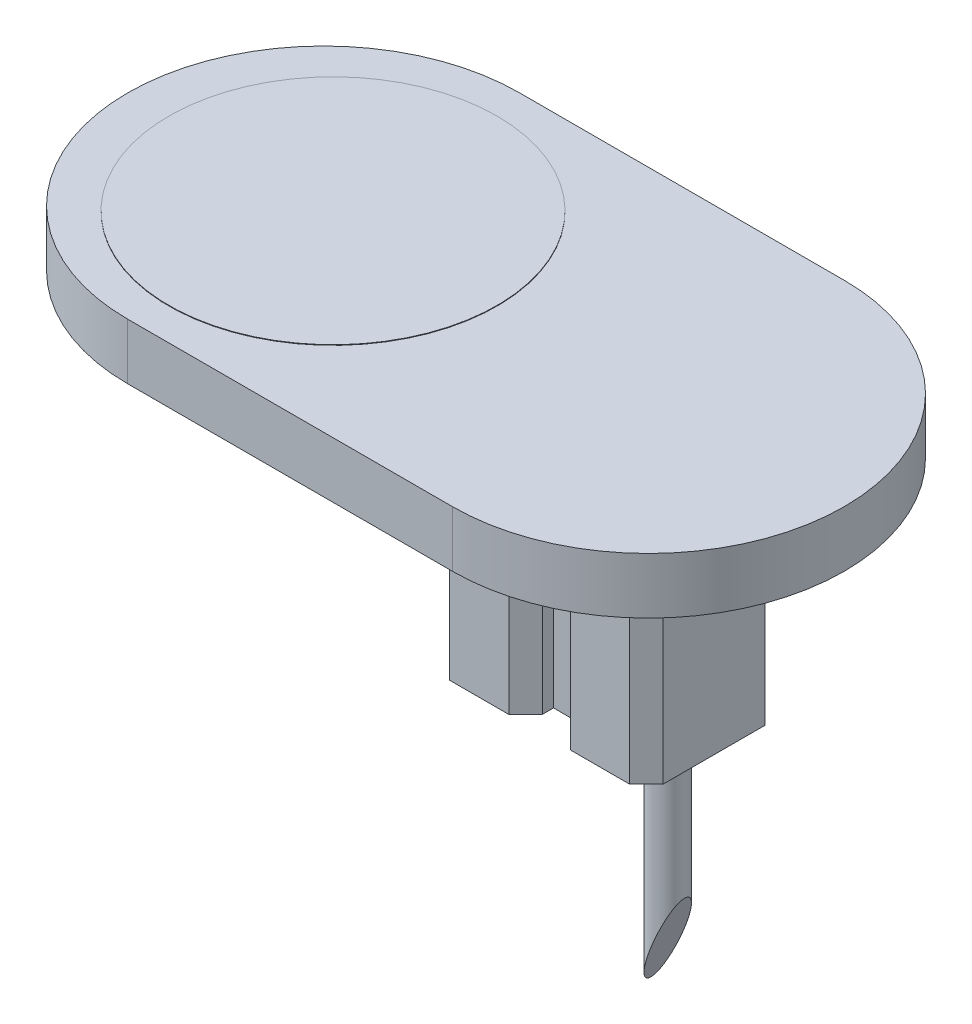
SolidWorks part; units mm, degrees
ref_plane "前视基准面" through (0, 0, 0) normal (0, 0, 1) x (1, 0, 0)
ref_plane "上视基准面" through (0, 0, 0) normal (0, 1, 0) x (1, 0, 0)
ref_plane "右视基准面" through (0, 0, 0) normal (1, 0, 0) x (0, 0, -1)
sketch "草图1" plane through (0, 0, 0) normal (0, 1, 0) x (1, 0, 0)
  line L0 (-8.8189, 0) -> (-3.0189, 0) construction
  line L1 (-8.8189, 3.5) -> (-3.0189, 3.5)
  line L2 (-8.8189, -3.5) -> (-3.0189, -3.5)
  arc A0 (-8.8189, 3.5) -> (-8.8189, -3.5) centre (-8.8189, 0) ccw
  arc A1 (-3.0189, -3.5) -> (-3.0189, 3.5) centre (-3.0189, 0) ccw
  point P3 (-5.9189, 0)
  dimension "D2" = 3.5
  dimension "D1" = 5.8
extrude "凸台-拉伸1" add sketch "草图1" along normal blind 1
sketch "草图2" plane through (0, 1, 0) normal (0, 1, 0) x (1, 0, 0)
  circle A0 centre (-8.6515, 0) radius 2.9305
extrude "凸台-拉伸2" add sketch "草图2" along normal blind 0.01 contours A0
sketch "草图3" plane through (0, 0, 0) normal (0, -1, 0) x (-1, 0, 0)
  line L0 (12.3189, 0) -> (5.6584, 0) construction
  line L1 (5.6584, -1.2107) -> (1.8446, -1.2107)
  line L2 (5.6584, -1.2107) -> (5.6584, 1.2107)
  line L3 (5.6584, 1.2107) -> (1.8446, 1.2107)
  line L4 (1.8446, -1.2107) -> (1.8446, 1.2107)
  arc A0 (8.8189, -3.5) -> (8.8189, 3.5) centre (8.8189, 0) ccw construction
extrude "凸台-拉伸3" add sketch "草图3" along normal blind 4
sketch "草图4" plane through (0, 0, -1.2107) normal (0, 0, -1) x (-1, 0, 0)
  line L0 (5.6584, -4) -> (1.8446, -4) construction
  line L1 (4.0015, -4) -> (3.5015, -4)
  line L2 (4.0015, -4) -> (4.0015, 0)
  line L3 (4.0015, 0) -> (3.5015, 0)
  line L4 (3.5015, -4) -> (3.5015, 0)
  line L5 (5.6584, 0) -> (1.8446, 0) construction
  line L6 (5.6584, -2) -> (4.0015, -2) construction
  line L7 (5.6584, -4) -> (5.6584, 0) construction
  line L8 (3.5015, -2) -> (1.8446, -2) construction
  line L9 (1.8446, -4) -> (1.8446, 0) construction
  dimension "D1" = 0.5
extrude "切除-拉伸1" cut sketch "草图4" against normal blind 0.3
sketch "草图5" plane through (0, 0, 1.2107) normal (0, 0, 1) x (1, 0, 0)
  line L1 (-3.5015, -4) -> (-4.0015, -4)
  line L2 (-3.5015, -4) -> (-3.5015, 0)
  line L3 (-3.5015, 0) -> (-4.0015, 0)
  line L4 (-4.0015, -4) -> (-4.0015, 0)
extrude "切除-拉伸2" cut sketch "草图5" against normal blind 0.5
chamfer "倒角1" distance 0.3 angle 45 8 edges at (-1.8446, -2, -1.2107) (-5.6584, -2, -1.2107) (-5.6584, -2, 1.2107) (-1.8446, -2, 1.2107) (-4.0015, -2, -1.2107) (-3.5015, -2, -1.2107) (-4.0015, -2, 1.2107) (-3.5015, -2, 1.2107)
sketch "草图6" plane through (0, -4, 0) normal (0, -1, 0) x (-1, 0, 0)
  line L0 (2.673, 0) -> (2.673, 1.2107) construction
  line L1 (3.2015, 1.2107) -> (2.1446, 1.2107) construction
  line L2 (2.673, 0) -> (1.8446, 0) construction
  line L3 (1.8446, 0.9107) -> (1.8446, -0.9107) construction
  circle A0 centre (2.673, 0) radius 0.3
  dimension "D1" = 0.6
extrude "凸台-拉伸4" add sketch "草图6" along normal blind 4
sketch "草图7" plane through (0, 0, 0) normal (0, 0, 1) x (1, 0, 0)
  line L0 (-2.973, -8) -> (-2.373, -6.4852)
  line L1 (-2.373, -8) -> (-2.373, -4) construction
  line L2 (-2.373, -6.4852) -> (-2.373, -8)
  line L3 (-2.373, -8) -> (-2.973, -8)
extrude "切除-拉伸3" cut sketch "草图7" against normal mid plane 4
